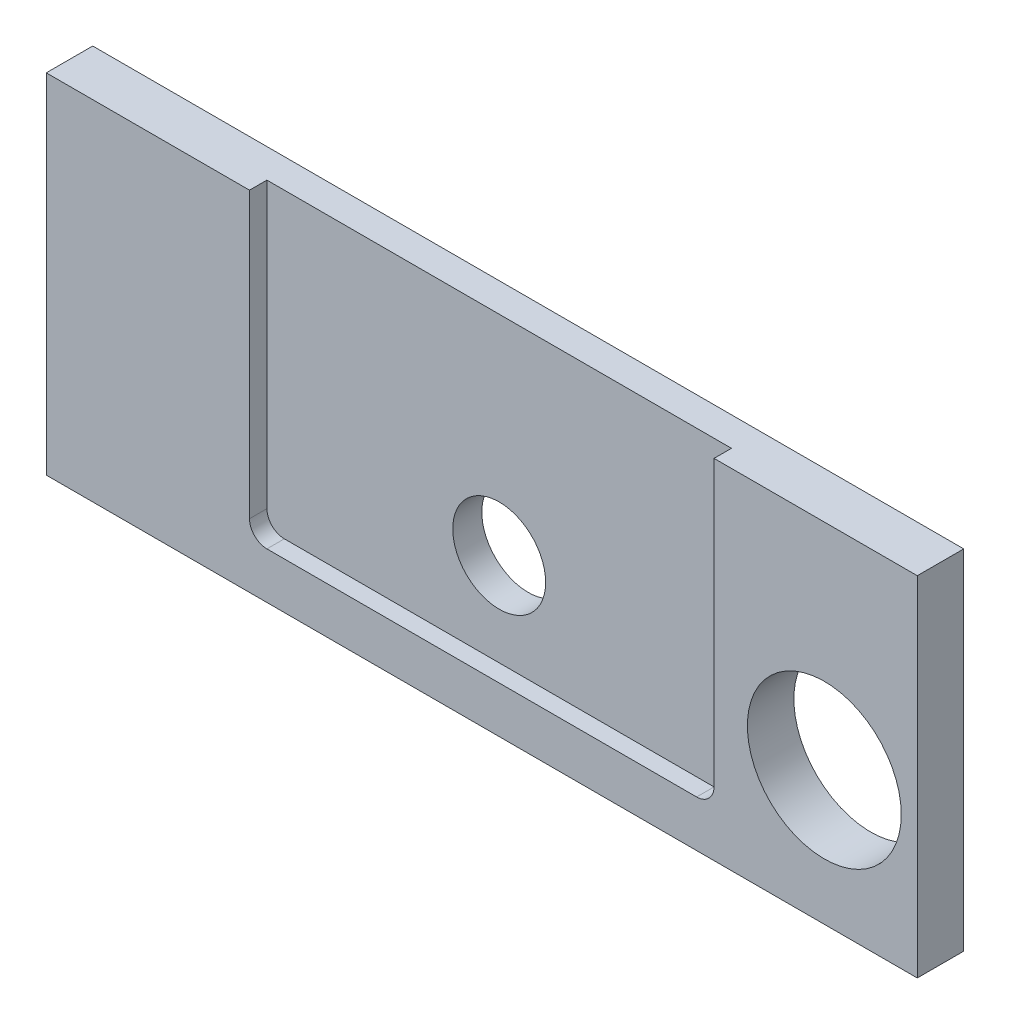
SolidWorks part; units mm, degrees
ref_plane "Front" through (0, 0, 0) normal (0, 0, 1) x (1, 0, 0)
ref_plane "Top" through (0, 0, 0) normal (0, 1, 0) x (1, 0, 0)
ref_plane "Right" through (0, 0, 0) normal (1, 0, 0) x (0, 0, -1)
sketch "Esquisse1" plane through (0, 0, 0) normal (0, 0, 1) x (1, 0, 0)
  line L1 (0, 0) -> (150, 0)
  line L2 (0, 0) -> (0, 60)
  line L3 (0, 60) -> (150, 60)
  line L4 (150, 0) -> (150, 60)
  dimension "D1" = 150
  dimension "D2" = 60
extrude "Boss.-Extru.1" add sketch "Esquisse1" along normal blind 8
sketch "Esquisse2" plane through (0, 0, 8) normal (0, 0, 1) x (1, 0, 0)
  line L0 (75, 0) -> (75, 60) construction
  line L1 (0, 0) -> (150, 0) construction
  line L2 (150, 60) -> (0, 60) construction
  line L3 (115, 60) -> (35, 60)
  line L4 (35, 60) -> (35, 0)
  line L5 (35, 0) -> (115, 0)
  line L6 (115, 60) -> (115, 0)
  dimension "D1" = 80
extrude "Enlèv. mat.-Extru.1" cut sketch "Esquisse2" against normal blind 3
sketch "Esquisse3" plane through (0, 0, 5) normal (0, 0, 1) x (1, 0, 0)
  line L0 (75, 0) -> (75, 24) construction
  line L1 (35, 0) -> (115, 0) construction
  circle A0 centre (75, 24) radius 8
  dimension "D1" = 16
  dimension "D2" = 24
extrude "Enlèv. mat.-Extru.2" cut sketch "Esquisse3" against normal through all both and the other way through all
sketch "Esquisse4" plane through (0, 0, 5) normal (0, 0, 1) x (1, 0, 0)
  line L0 (115, 0) -> (115, 60) construction
  line L1 (35, 0) -> (115, 0)
  line L2 (35, 0) -> (35, 8)
  line L3 (35, 8) -> (115, 8)
  line L4 (115, 0) -> (115, 8)
  dimension "D1" = 8
extrude "Boss.-Extru.2" add sketch "Esquisse4" along normal up to vertex (3 mm away) up to point (115, 60, 8)
fillet "Congé1" radius 3 2 edges at (35, 8, 6.5) (115, 8, 6.5)
sketch "Esquisse5" plane through (0, 0, 8) normal (0, 0, 1) x (1, 0, 0)
  line L0 (133.9915, 23) -> (75, 24) construction
  line L1 (0, 0) -> (150, 0) construction
  circle A0 centre (133.9915, 23) radius 13.25
  dimension "D2" = 23
  dimension "D3" = 26.5
  dimension "D1" = 59
extrude "Enlèv. mat.-Extru.3" cut sketch "Esquisse5" against normal through all
